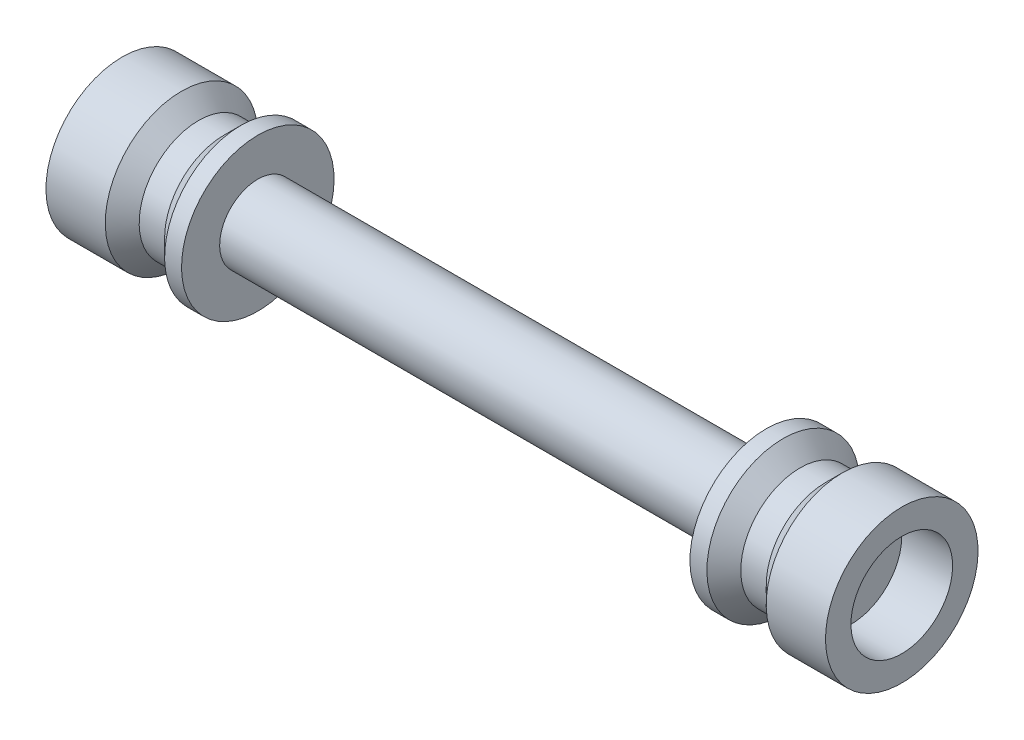
SolidWorks part; units mm, degrees
ref_plane "Front" through (0, 0, 0) normal (0, 0, 1) x (1, 0, 0)
ref_plane "Top" through (0, 0, 0) normal (0, 1, 0) x (1, 0, 0)
ref_plane "Right" through (0, 0, 0) normal (1, 0, 0) x (0, 0, -1)
sketch "Esquisse1" plane through (0, 0, 0) normal (0, 0, 1) x (1, 0, 0)
  line L0 (0, 0) -> (0, 11.3185) construction
  line L1 (0, 0) -> (-20, 0)
  line L2 (-20, 0) -> (-20, 3)
  line L3 (-20, 3) -> (-23, 3)
  line L4 (-23, 3) -> (-23, 4.5)
  line L5 (-23, 4.5) -> (-19.5, 4.5)
  line L6 (-19.5, 4.5) -> (-18.5, 3.5)
  line L7 (-18.5, 3.5) -> (-17, 3.5)
  line L8 (-17, 3.5) -> (-16, 4.5)
  line L9 (-16, 4.5) -> (-15, 4.5)
  line L10 (-15, 4.5) -> (-15, 2.25)
  line L11 (-15, 2.25) -> (15, 2.25)
  line L12 (15, 4.5) -> (15, 2.25)
  line L13 (16, 4.5) -> (15, 4.5)
  line L14 (17, 3.5) -> (16, 4.5)
  line L15 (18.5, 3.5) -> (17, 3.5)
  line L16 (19.5, 4.5) -> (18.5, 3.5)
  line L17 (23, 4.5) -> (19.5, 4.5)
  line L18 (23, 3) -> (23, 4.5)
  line L19 (20, 3) -> (23, 3)
  line L20 (20, 0) -> (20, 3)
  line L21 (0, 0) -> (20, 0)
  line L22 (0, 0) -> (-29.7186, 0) construction
  point P15 (0, 2.25)
  dimension "D1" = 30
  dimension "D2" = 4.5
  dimension "D3" = 9
  dimension "D4" = 7
  dimension "D5" = 45
  dimension "D6" = 8
  dimension "D7" = 1
  dimension "D8" = 1.5
  dimension "D9" = 1.5
  dimension "D10" = 3
revolve "Revolution1" add sketch "Esquisse1" angle 360 about L22
chamfer "Chamfer1" [suppressed] distance 0.5 angle 45
sketch3d "3DSketch1" plane through (0, 0, 0) normal (0, 0, 1) x (1, 0, 0)
sketch "Sketch3" plane through (-15, 0, 0) normal (-1, 0, 0) x (0, 0, 1)
  point P0 (0, 0)
sketch3d "3DSketch2" plane through (0, 0, 0) normal (0, 0, 1) x (1, 0, 0)
sketch "Sketch4" plane through (15, 0, 0) normal (1, 0, 0) x (0, 0, -1)
  point P0 (0, 0)
sketch3d "3DSketch3" plane through (0, 0, 0) normal (0, 0, 1) x (1, 0, 0)
  dimension "D1" = 5
sketch3d "3DSketch4" plane through (0, 0, 0) normal (0, 0, 1) x (1, 0, 0)
  dimension "D1" = 5
sketch "Sketch5" plane through (10, 0, 0) normal (-1, 0, 0) x (0, 0, 1)
  point P0 (0, 0)
